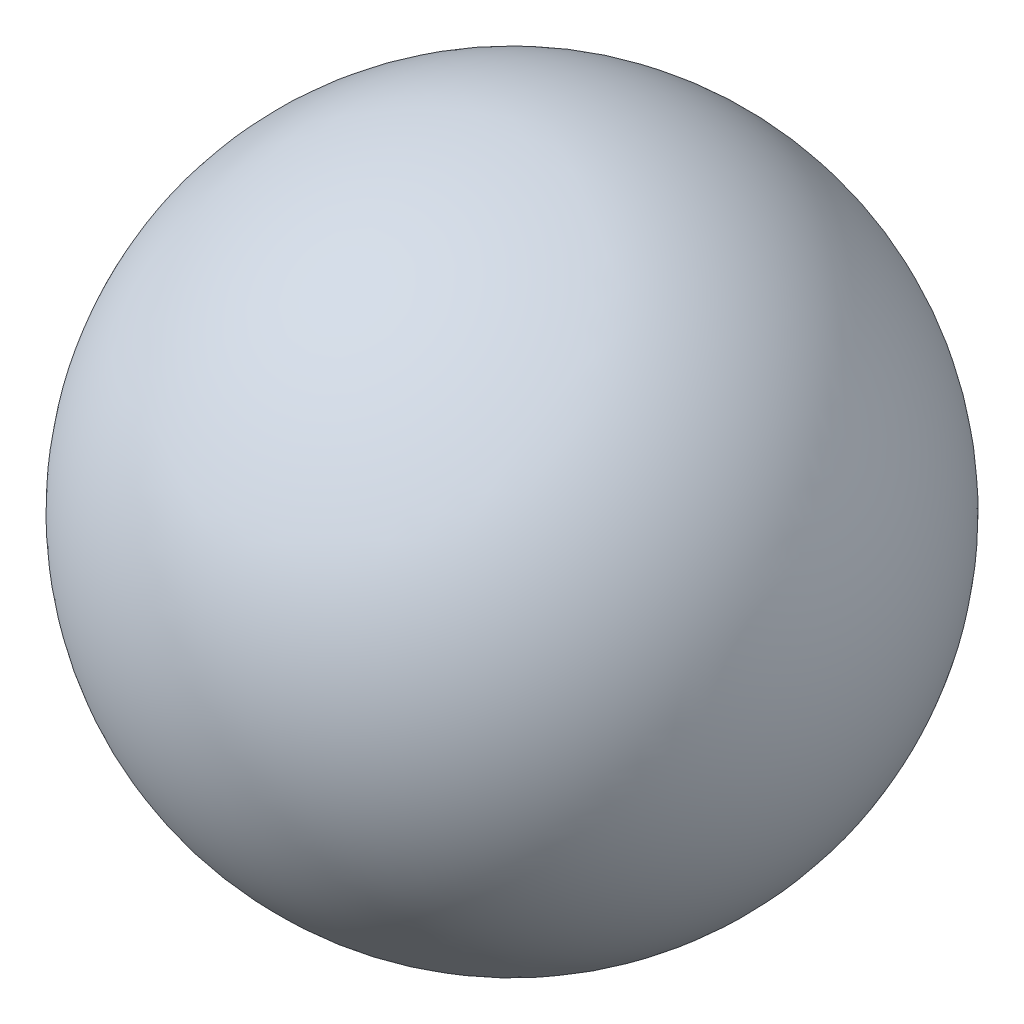
SolidWorks part; units mm, degrees
ref_plane "Front Plane" through (0, 0, 0) normal (0, 0, 1) x (1, 0, 0)
ref_plane "Top Plane" through (0, 0, 0) normal (0, 1, 0) x (1, 0, 0)
ref_plane "Right Plane" through (0, 0, 0) normal (1, 0, 0) x (0, 0, -1)
sketch "Sketch1" plane through (0, 0, 0) normal (0, 1, 0) x (1, 0, 0)
  line L0 (-1.607, 0) -> (1.607, 0) construction
  line L1 (-1.607, 0) -> (1.607, 0)
  circle A0 centre (0, 0) radius 1.607
  dimension "D1" = 3.214
revolve "Revolve1" add sketch "Sketch1" angle 360 about L1 region at (0, 0, -0.682)
equation "\"bearing_21_OD\"= 21mm"
equation "\"pin_cirlce_diameter\"= 75mm"
equation "\"pin_diam\"= 6mm"
equation "\"gear_thickness\"= 4mm"
equation "\"ball_bearing_diam\"= 3.214mm"
equation "\"bearing_21_outer_clearance\"= 0.127mm'change this"
equation "\"bearing_15_OD\"= 15mm"
equation "\"bearing_15_outer_clearance\"= 0mm'change this"
equation "\"thrust_bearing_thickness\"= 5mm'measure this irl and change"
equation "\"D1@Sketch1\"=\"ball_bearing_diam\""
